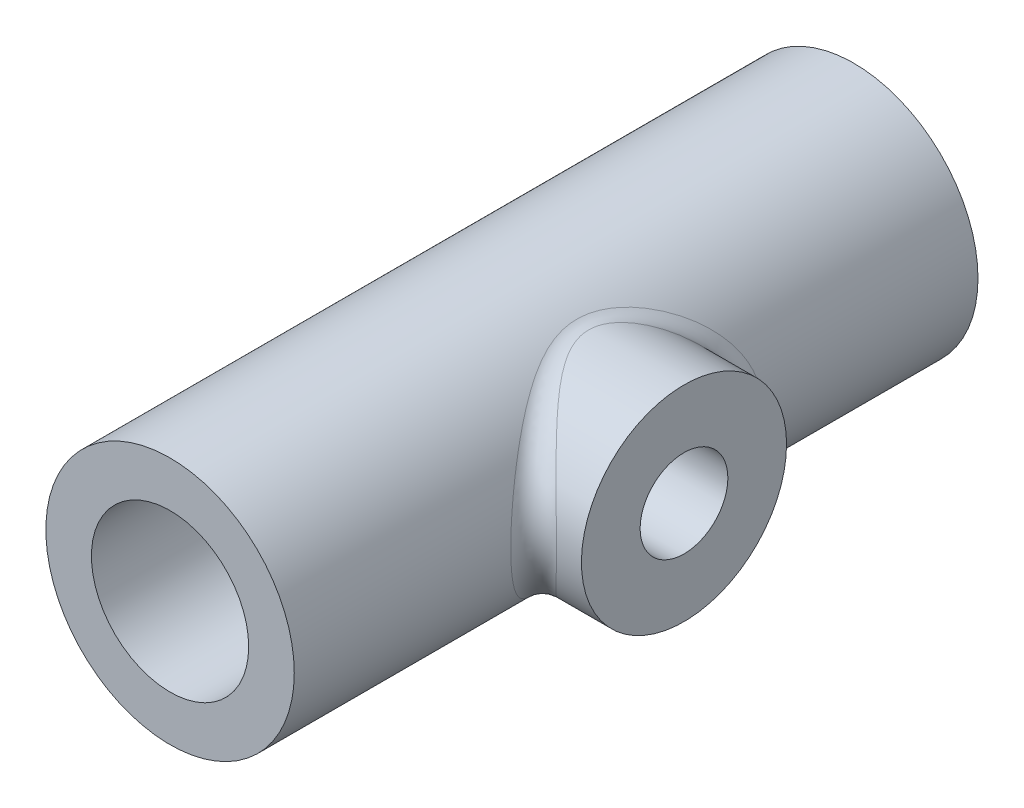
SolidWorks part; units mm, degrees
ref_plane "Front Plane" through (0, 0, 0) normal (0, 0, 1) x (1, 0, 0)
ref_plane "Top Plane" through (0, 0, 0) normal (0, 1, 0) x (1, 0, 0)
ref_plane "Right Plane" through (0, 0, 0) normal (1, 0, 0) x (0, 0, -1)
sketch "Sketch24" plane through (0, 0, 0) normal (0, 0, 1) x (1, 0, 0)
  circle A0 centre (0, 0) radius 13.843
  dimension "D1" = 27.686
extrude "Boss-Extrude3" add sketch "Sketch24" along normal blind 76.2
sketch "Sketch25" plane through (0, 0, 0) normal (1, 0, 0) x (0, 0, -1)
  circle A0 centre (-38.1, 0) radius 11.43
  dimension "D1" = 22.86
extrude "Boss-Extrude4" add sketch "Sketch25" along normal blind 19.177
sketch "Sketch26" plane through (0, 0, 0) normal (1, 0, 0) x (0, 0, -1)
  circle A0 centre (-38.1, 0) radius 4.8895
  dimension "D1" = 9.779
extrude "Cut-Extrude3" cut sketch "Sketch26" along normal blind 22.225
ref_plane "Plane2" through (0, 0, 82.55) normal (0, 0, 1) x (1, 0, 0)
sketch "Sketch27" plane through (0, 0, 82.55) normal (0, 0, 1) x (1, 0, 0)
  circle A0 centre (0, 0) radius 8.763
  arc A1 (7.8092, -11.43) -> (7.8092, 11.43) centre (0, 0) ccw construction
  dimension "D1" = 5.08
extrude "Cut-Extrude4" cut sketch "Sketch27" against normal through all both and the other way through all
fillet "Fillet1" radius 2.54 1 edges at (13.8257, 0.692, 26.691)
sketch "Sketch28" plane through (0, 0, 0) normal (0, 0, -1) x (-1, 0, 0)
  line L0 (-8.763, 16.7729) -> (-8.763, -16.7729) construction
  line L1 (0, 0) -> (-31.1486, 0) construction
  circle A1 centre (0, 0) radius 8.763 construction
  point P7 (-8.763, 0)
